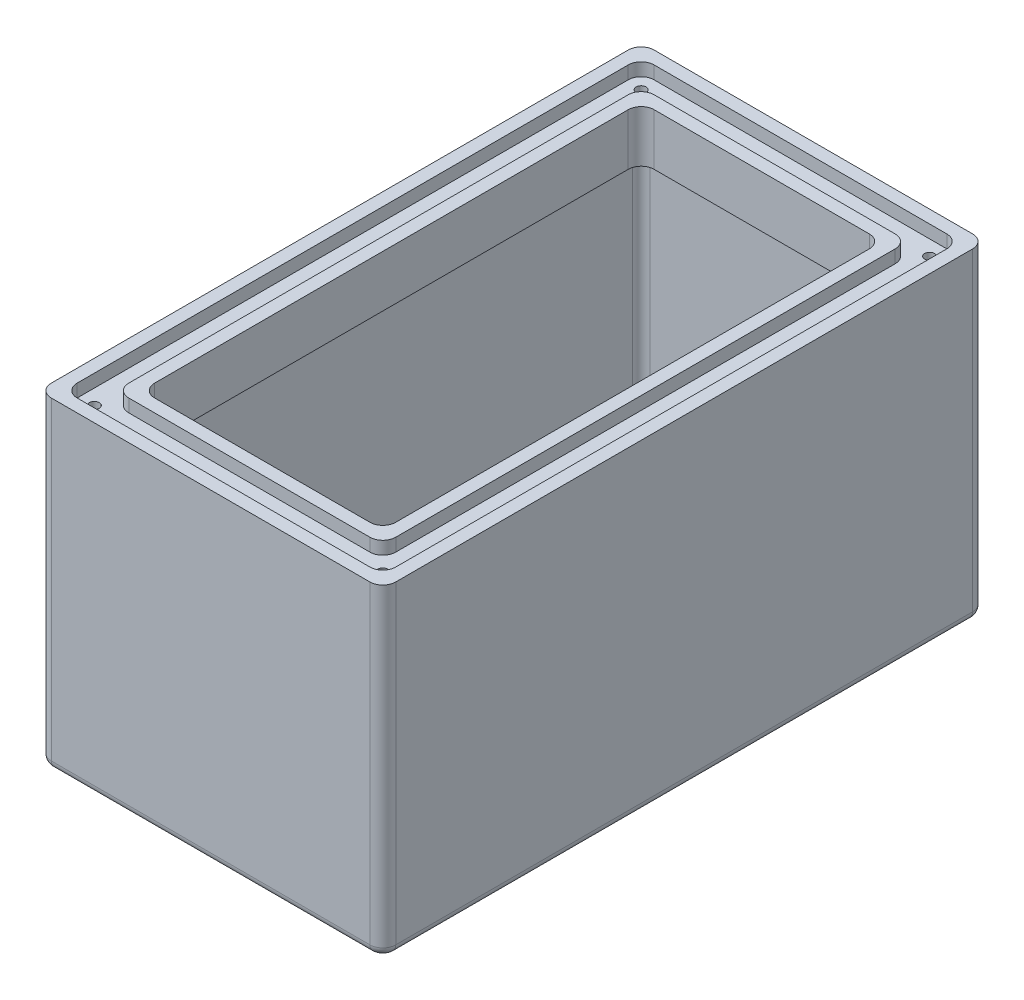
SolidWorks part; units mm, degrees
ref_plane "Front Plane" through (0, 0, 0) normal (0, 0, 1) x (1, 0, 0)
ref_plane "Top Plane" through (0, 0, 0) normal (0, 1, 0) x (1, 0, 0)
ref_plane "Right Plane" through (0, 0, 0) normal (1, 0, 0) x (0, 0, -1)
sketch "Sketch1" plane through (0, 0, 0) normal (0, 1, 0) x (1, 0, 0)
  line L1 (0, 0) -> (80, 0)
  line L2 (0, 0) -> (0, 140)
  line L3 (0, 140) -> (80, 140)
  line L4 (80, 0) -> (80, 140)
  dimension "D1" = 140
  dimension "D2" = 80
extrude "Boss-Extrude1" add sketch "Sketch1" along normal blind 3
sketch "Sketch2" plane through (0, 3, 0) normal (0, 1, 0) x (1, 0, 0)
  line L1 (0, 140) -> (80, 140)
  line L2 (0, 140) -> (0, 0)
  line L3 (0, 0) -> (80, 0)
  line L4 (80, 140) -> (80, 0)
  line L5 (3, 137) -> (77, 137)
  line L6 (3, 137) -> (3, 3)
  line L7 (3, 3) -> (77, 3)
  line L8 (77, 137) -> (77, 3)
  dimension "D1" = 3
  dimension "D2" = 3
  dimension "D3" = 3
  dimension "D4" = 3
extrude "Boss-Extrude2" add sketch "Sketch2" along normal blind 60
fillet "Fillet1" radius 2 8 edges at (40, 3, -3) (77, 3, -70) (3, 3, -70) (40, 3, -137) (77, 33, -3) (3, 33, -3) (77, 33, -137) (3, 33, -137)
fillet "Fillet2" radius 2 4 edges at (40, 0, -140) (0, 0, -70) (40, 0, 0) (80, 0, -70)
sketch "Sketch6" plane through (0, 63, 0) normal (0, 1, 0) x (1, 0, 0)
  line L1 (0, 140) -> (80, 140)
  line L2 (0, 140) -> (0, 0)
  line L3 (0, 0) -> (80, 0)
  line L4 (80, 140) -> (80, 0)
  line L5 (15, 128) -> (65, 128)
  line L6 (12, 125) -> (12, 15)
  line L7 (15, 12) -> (65, 12)
  line L8 (68, 125) -> (68, 15)
  arc A0 (65, 12) -> (68, 15) centre (65, 15) ccw
  arc A1 (12, 15) -> (15, 12) centre (15, 15) ccw
  arc A2 (65, 128) -> (68, 125) centre (65, 125) cw
  arc A3 (15, 128) -> (12, 125) centre (15, 125) ccw
  dimension "D5" = 3
  dimension "D1" = 12
  dimension "D2" = 12
  dimension "D3" = 12
  dimension "D4" = 12
extrude "Boss-Extrude3" add sketch "Sketch6" along normal blind 12
sketch "Sketch7" plane through (0, 75, 0) normal (0, 1, 0) x (1, 0, 0)
  line L0 (80, 140) -> (0, 140) construction
  line L1 (6, 137) -> (74, 137)
  line L2 (3, 134) -> (3, 6)
  line L3 (6, 3) -> (74, 3)
  line L4 (77, 134) -> (77, 6)
  line L5 (80, 0) -> (80, 140) construction
  line L6 (0, 0) -> (80, 0) construction
  line L7 (0, 140) -> (0, 0) construction
  line L13 (12, 131) -> (68, 131)
  line L14 (9, 128) -> (9, 12)
  line L15 (12, 9) -> (68, 9)
  line L16 (71, 128) -> (71, 12)
  arc A0 (3, 6) -> (6, 3) centre (6, 6) ccw
  arc A1 (74, 3) -> (77, 6) centre (74, 6) ccw
  arc A2 (74, 137) -> (77, 134) centre (74, 134) cw
  arc A3 (6, 137) -> (3, 134) centre (6, 134) ccw
  arc A7 (9, 12) -> (12, 9) centre (12, 12) ccw
  arc A8 (68, 9) -> (71, 12) centre (68, 12) ccw
  arc A9 (68, 131) -> (71, 128) centre (68, 128) cw
  arc A10 (12, 131) -> (9, 128) centre (12, 128) ccw
  dimension "D5" = 3
  dimension "D6" = 6
  dimension "D10" = 3
  dimension "D1" = 3
  dimension "D2" = 3
  dimension "D3" = 3
  dimension "D4" = 3
  dimension "D7" = 6
  dimension "D8" = 6
  dimension "D9" = 6
extrude "Cut-Extrude1" cut sketch "Sketch7" against normal blind 3
sketch "Sketch8" plane through (0, 72, 0) normal (0, 1, 0) x (1, 0, 0)
  line L0 (0, 0) -> (80, 0) construction
  line L1 (0, 140) -> (0, 0) construction
  line L2 (80, 0) -> (80, 140) construction
  line L3 (80, 140) -> (0, 140) construction
  circle A0 centre (6.5, 6.5) radius 1.15
  circle A1 centre (73.5, 6.5) radius 1.15
  circle A2 centre (73.5, 133.5) radius 1.15
  circle A3 centre (6.5, 133.5) radius 1.15
  dimension "D1" = 2.3
  dimension "D2" = 2.3
  dimension "D3" = 2.3
  dimension "D4" = 2.3
  dimension "D5" = 6.5
  dimension "D6" = 6.5
  dimension "D7" = 6.5
  dimension "D8" = 6.5
  dimension "D9" = 6.5
  dimension "D10" = 6.5
  dimension "D11" = 6.5
  dimension "D12" = 6.5
extrude "Cut-Extrude2" cut sketch "Sketch8" against normal blind 6
fillet "Fillet3" radius 3 8 edges at (0.5858, 0.5858, -139.4142) (79.4142, 0.5858, -139.4142) (79.4142, 0.5858, -0.5858) (0.5858, 0.5858, -0.5858) (0, 38.5, -140) (80, 38.5, -140) (80, 38.5, 0) (0, 38.5, 0)
